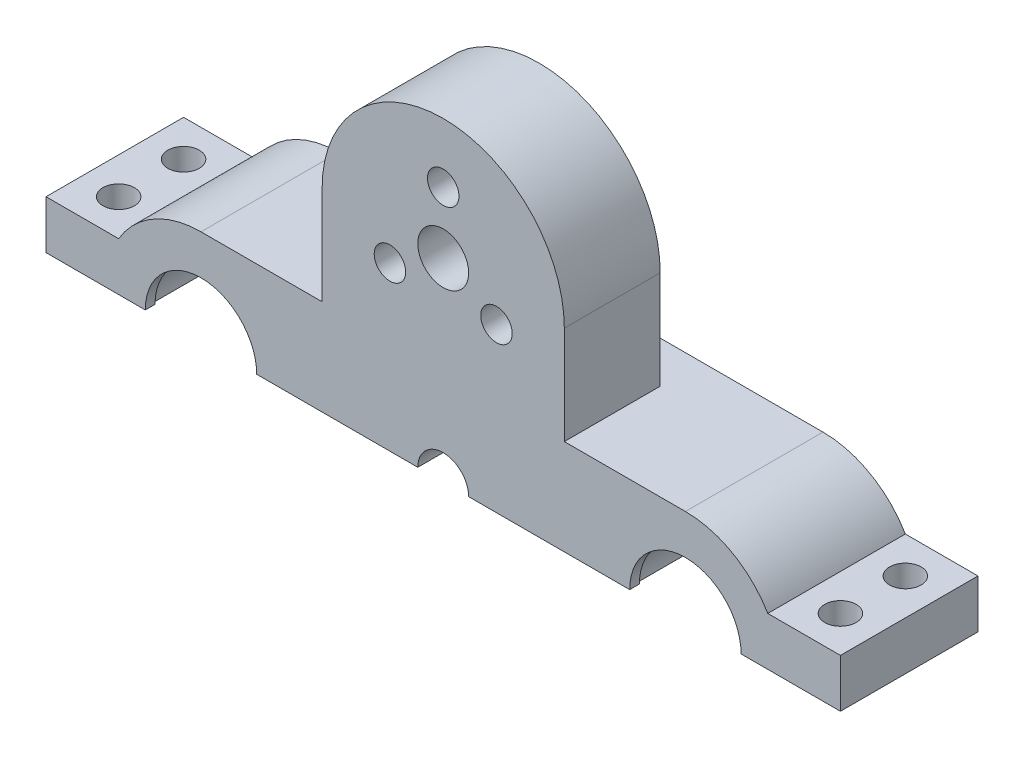
SolidWorks part; units mm, degrees
ref_plane "Front Plane" through (0, 0, 0) normal (0, 0, 1) x (1, 0, 0)
ref_plane "Top Plane" through (0, 0, 0) normal (0, 1, 0) x (1, 0, 0)
ref_plane "Right Plane" through (0, 0, 0) normal (1, 0, 0) x (0, 0, -1)
sketch "Sketch1" plane through (0, 0, 0) normal (0, 0, 1) x (1, 0, 0)
  line L1 (-41, 0) -> (41, 0)
  line L2 (-41, 0) -> (-41, 25)
  line L3 (-41, 25) -> (41, 25)
  line L4 (41, 0) -> (41, 25)
  point P5 (0, 0)
  dimension "D1" = 25
  dimension "D2" = 82
extrude "Boss-Extrude1" add sketch "Sketch1" along normal blind 14.2
sketch "Sketch2" plane through (0, 0, 0) normal (0, 0, -1) x (-1, 0, 0)
  line L0 (41, 0) -> (-41, 0) construction
  line L1 (-31, 0) -> (-19, 0)
  line L2 (19, 0) -> (31, 0)
  arc A0 (-31, 0) -> (-19, 0) centre (-25, 0) cw
  arc A1 (31, 0) -> (19, 0) centre (25, 0) ccw
  dimension "D1" = 6
  dimension "D3" = 6
  dimension "D2" = 10
  dimension "D4" = 10
extrude "Cut-Extrude3" cut sketch "Sketch2" against normal up to surface (14.2 mm away) up to face at (0, 12.5, 14.2)
sketch "Sketch4" plane through (0, 0, 0) normal (0, 0, -1) x (-1, 0, 0)
  line L0 (-30.75, 0) -> (-31, 0)
  line L1 (-19.25, 0) -> (-19, 0)
  line L2 (19, 0) -> (19.25, 0)
  line L3 (31, 0) -> (30.75, 0)
  line L4 (19, 0) -> (-19, 0) construction
  arc A0 (-31, 0) -> (-19, 0) centre (-25, 0) cw
  arc A1 (-30.75, 0) -> (-19.25, 0) centre (-25, 0) cw
  arc A2 (19, 0) -> (31, 0) centre (25, 0) cw
  arc A3 (19.25, 0) -> (30.75, 0) centre (25, 0) cw
  dimension "D1" = 5.75
extrude "Boss-Extrude2" add sketch "Sketch4" against normal blind 1
extrude "Boss-Extrude3" add sketch "Sketch4<2>" against normal blind 1 from offset 13.2 offset against normal yes
sketch "Sketch4<2>" plane through (0, 0, 0) normal (0, 0, -1) x (-1, 0, 0) same geometry as "Sketch4"
sketch "Sketch5" plane through (0, 0, 0) normal (0, 0, -1) x (-1, 0, 0)
  line L0 (19.25, 0) -> (-19.25, 0) construction
  line L1 (-6.5, 0) -> (6.5, 0)
  arc A0 (6.5, 0) -> (-6.5, 0) centre (0, 0) ccw
  dimension "D1" = 6.5
extrude "Cut-Extrude4" cut sketch "Sketch5" against normal blind 3.25 from offset 6.45 offset against normal yes
sketch "Sketch6" plane through (0, 0, 14.2) normal (0, 0, -1) x (-1, 0, 0)
  line L0 (19.25, 0) -> (-19.25, 0) construction
  line L1 (-2.625, 0) -> (2.625, 0)
  arc A0 (2.625, 0) -> (-2.625, 0) centre (0, 0) ccw
  dimension "D1" = 2.625
extrude "Cut-Extrude5" cut sketch "Sketch6" against normal up to surface (-7.75 mm away) up to face at (0, 3.25, 6.45)
sketch "Sketch7" plane through (0, 0, 0) normal (0, 0, -1) x (-1, 0, 0)
  line L0 (-41, 5) -> (-33.5, 5)
  line L2 (-25, 9.8615) -> (25, 9.8615)
  line L3 (33.5, 5) -> (41, 5)
  line L5 (-30.75, 0) -> (-41, 0) construction
  line L6 (-41, 0) -> (-41, 25) construction
  line L7 (-41, 5) -> (-41, 25)
  line L8 (-41, 25) -> (41, 25)
  line L9 (41, 25) -> (41, 5)
  arc A0 (-33.5, 5) -> (-25, 9.8615) centre (-25, 0) cw
  arc A1 (25, 9.8615) -> (33.5, 5) centre (25, 0) cw
  arc A2 (-19.25, 0) -> (-30.75, 0) centre (-25, 0) ccw construction
  arc A3 (30.75, 0) -> (19.25, 0) centre (25, 0) ccw construction
  dimension "D2" = 7.5
  dimension "D1" = 5
extrude "Cut-Extrude6" cut sketch "Sketch7" against normal up to surface (14.2 mm away) up to face at (0, 6.4125, 14.2)
sketch "Sketch8" plane through (0, 5, 0) normal (0, 1, 0) x (1, 0, 0)
  line L0 (41, 0) -> (33.5, 0) construction
  line L1 (41, -14.2) -> (41, 0) construction
  line L2 (33.5, -14.2) -> (41, -14.2) construction
  line L3 (0, -7.81) -> (0, 7.81) construction
  circle A0 centre (37.25, -3.75) radius 1.625
  circle A1 centre (37.25, -10.45) radius 1.625
  circle A2 centre (-37.25, -3.75) radius 1.625
  circle A3 centre (-37.25, -10.45) radius 1.625
  dimension "D1" = 3.25
  dimension "D2" = 3.75
  dimension "D3" = 3.75
  dimension "D4" = 3.75
  dimension "D5" = 3.75
extrude "Cut-Extrude7" cut sketch "Sketch8" against normal up to surface (5 mm away) up to face at (33.375, 0, 7.1)
sketch "Sketch10" plane through (0, 0, 14.2) normal (0, 0, 1) x (1, 0, 0)
  line L0 (-25, 9.8615) -> (25, 9.8615) construction
  line L1 (-12.5, 20) -> (12.5, 20)
  line L2 (-12.5, 20) -> (-12.5, 9.8615)
  line L3 (12.5, 20) -> (12.5, 9.8615)
  line L4 (12.5, 9.8615) -> (-12.5, 9.8615)
  line L5 (-19.25, 0) -> (19.25, 0) construction
  arc A0 (12.5, 20) -> (-12.5, 20) centre (0, 20) ccw
  point P7 (0, 20)
  line M12 (25, 9.8615) -> (-25, 9.8615)
  dimension "D1" = 12.5
  dimension "D2" = 20
extrude "Boss-Extrude4" add sketch "Sketch10" against normal blind 9.9 contours L3 L1 L2 M12 | L1 A0 region at (0, 25.3052, 14.2) region at (0, 14.9308, 14.2)
sketch "Sketch11" plane through (0, 0, 4.3) normal (0, 0, -1) x (-1, 0, 0)
  circle A0 centre (0, 20) radius 9.75
  arc A2 (12.5, 20) -> (-12.5, 20) centre (0, 20) ccw construction
  dimension "D1" = 19.5
extrude "Cut-Extrude8" cut sketch "Sketch11" against normal blind 4
sketch "Sketch12" plane through (0, 0, 8.3) normal (0, 0, -1) x (-1, 0, 0)
  line L0 (0, 29.75) -> (0, 10.25) construction
  line L1 (-9.75, 20) -> (9.75, 20) construction
  circle A0 centre (0, 26.35) radius 1.625
  circle A1 centre (0, 20) radius 9.75 construction
  circle A2 centre (0, 20) radius 9.75 construction
  point P11 (0, 20)
  dimension "D1" = 3.25
  dimension "D2" = 6.35
extrude "Cut-Extrude9" cut sketch "Sketch12" against normal up to surface (5.9 mm away) up to face at (0, 7.1295, 14.2)
pattern_circular "CirPattern1" count 3 over 360 about axis through (0, 20, 4.3) along (0, 0, -1) of "Cut-Extrude9"
sketch "Sketch13" plane through (0, 0, 8.3) normal (0, 0, -1) x (-1, 0, 0)
  circle A0 centre (0, 20) radius 2.625
  dimension "D1" = 5.25
extrude "Cut-Extrude10" cut sketch "Sketch13" against normal up to surface (5.9 mm away) up to face at (3.8743, 16.825, 14.2)
